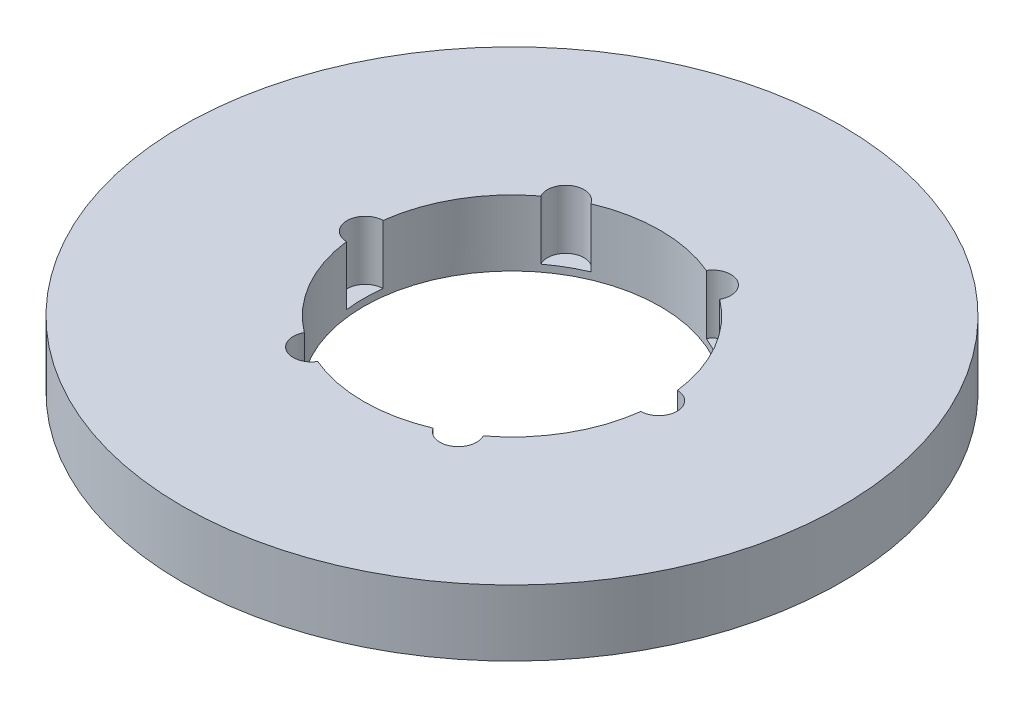
SolidWorks part; units mm, degrees
ref_plane "Front Plane" through (0, 0, 0) normal (0, 0, 1) x (1, 0, 0)
ref_plane "Top Plane" through (0, 0, 0) normal (0, 1, 0) x (1, 0, 0)
ref_plane "Right Plane" through (0, 0, 0) normal (1, 0, 0) x (0, 0, -1)
sketch "Sketch1" plane through (0, 0, 0) normal (0, 1, 0) x (1, 0, 0)
  circle A0 centre (0, 0) radius 50
  dimension "FLANGE_OD" = 100
extrude "Boss-Extrude1" add sketch "Sketch1" along normal blind 10
sketch "Sketch2" plane through (0, 0, 0) normal (0, 1, 0) x (1, 0, 0)
  circle A0 centre (0, 0) radius 22.5
  dimension "BORE_D" = 45
extrude "Cut-Extrude1" cut sketch "Sketch2" along normal through all
sketch "Sketch3" plane through (0, 10, 0) normal (0, 1, 0) x (1, 0, 0)
  circle A0 centre (0, 0) radius 22.2679 construction
  circle A1 centre (-22.2679, 0) radius 2.7797
  dimension "BOLT_D" = 5.5594
  dimension "BOLT_PCD" = 44.5358
extrude "Cut-Extrude2" cut sketch "Sketch3" against normal blind 8.9503
pattern_circular "CirPattern1" count 6 over 360 about axis through (0, 0, 0) along (0, 1, 0) of "Cut-Extrude2"
